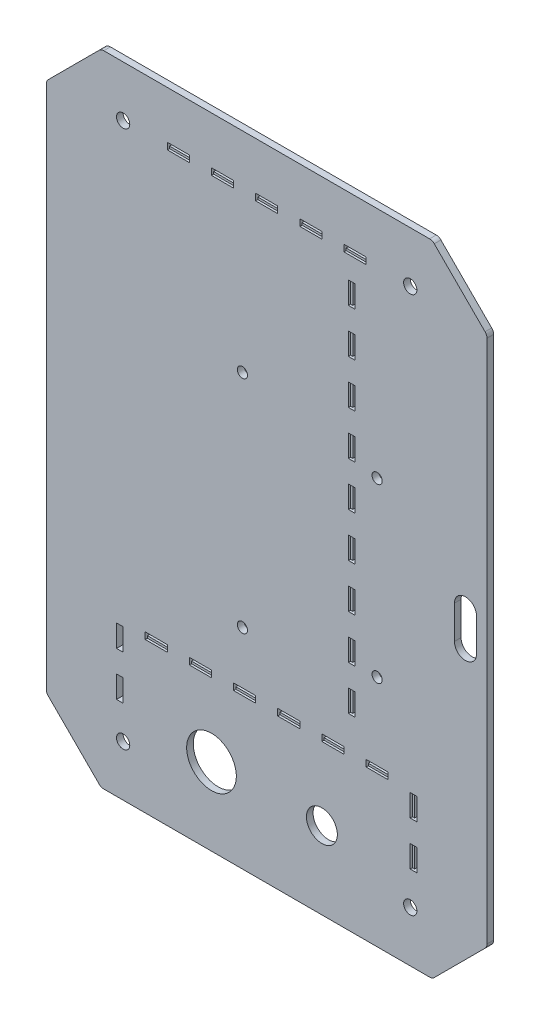
SolidWorks part; units mm, degrees
ref_plane "Plan de face" through (0, 0, 0) normal (0, 0, 1) x (1, 0, 0)
ref_plane "Plan de dessus" through (0, 0, 0) normal (0, 1, 0) x (1, 0, 0)
ref_plane "Plan de droite" through (0, 0, 0) normal (1, 0, 0) x (0, 0, -1)
sketch "Esquisse1" plane through (0, 0, 0) normal (0, 0, 1) x (1, 0, 0)
  line L0 (-99.7487, 120) -> (-75, 144.7487)
  line L1 (-75, 144.7487) -> (75, 144.7487)
  line L2 (-99.7487, 120) -> (-99.7487, -120)
  line L3 (-75, -144.7487) -> (75, -144.7487)
  line L4 (99.7487, 120) -> (99.7487, -120)
  line L5 (75, 144.7487) -> (99.7487, 120)
  line L6 (99.7487, -120) -> (75, -144.7487)
  line L7 (-87.3744, 132.3744) -> (87.3744, -132.3744) construction
  line L8 (-99.7487, -120) -> (-75, -144.7487)
  line L9 (-87.3744, -132.3744) -> (87.3744, 132.3744) construction
  point P0 (0, 0)
  point P14 (0, 0)
  dimension "D1" = 240
  dimension "D2" = 150
  dimension "D3" = 35
  dimension "D4" = 135
  dimension "D5" = 135
extrude "Base" add sketch "Esquisse1" along normal blind 3
sketch "Esquisse2" plane through (0, 0, 3) normal (0, 0, 1) x (1, 0, 0)
  line L0 (-99.7487, 0) -> (99.7487, 0) construction
  line L1 (-99.7487, 120) -> (-99.7487, -120) construction
  line L2 (99.7487, -120) -> (99.7487, 120) construction
  line L3 (0, 144.7487) -> (0, -144.7487) construction
  line L4 (75, 144.7487) -> (-75, 144.7487) construction
  line L5 (-75, -144.7487) -> (75, -144.7487) construction
  line L11 (-67.1213, 123.8701) -> (-62.8787, 119.6274) construction
  line L12 (-67.1213, 119.6274) -> (-62.8787, 123.8701) construction
  circle A0 centre (-65, 121.7487) radius 3
  circle A1 centre (65, 121.7487) radius 3
  circle A2 centre (65, -121.7487) radius 3
  circle A3 centre (-65, -121.7487) radius 3
  point P12 (-65, 121.7487)
  dimension "D5" = 6
  dimension "D3" = 23
  dimension "D4" = 65
extrude "Perçage profilé" cut sketch "Esquisse2" against normal blind 5
sketch "Esquisse3" plane through (0, 0, 0) normal (0, 0, -1) x (-1, 0, 0)
  line L0 (45, 0) -> (-45, 0) construction
  line L6 (75, -144.7487) -> (-75, -144.7487) construction
  line L7 (45, 45) -> (45, -45) construction
  line L8 (45, -45) -> (-45, -45) construction
  line L9 (-45, -45) -> (-45, 45) construction
  line L10 (-45, 45) -> (45, 45) construction
  line L11 (-99.7487, -120) -> (-99.7487, 120) construction
  circle A4 centre (-50, 39) radius 2.3
  circle A5 centre (11, 50) radius 2.3
  circle A6 centre (-50, -39) radius 2.3
  circle A7 centre (11, -50) radius 2.3
  point P16 (-99.7487, 0)
  point P19 (0, -144.7487)
  point P20 (0, 0)
  point P22 (0, -45)
  dimension "D3" = 4.6
  dimension "D8" = 4.6
  dimension "D1" = 90
  dimension "D2" = 90
  dimension "D4" = 5
  dimension "D5" = 6
  dimension "D6" = 34
  dimension "D7" = 5
extrude "Perçage Lidar" cut sketch "Esquisse3" against normal through all
sketch "Esquisse4" plane through (0, 0, 0) normal (0, 0, -1) x (-1, 0, 0)
  line L0 (75, -144.7487) -> (-75, -144.7487) construction
  line L1 (0, -144.7487) -> (0, -86.7053) construction
  circle A0 centre (25, -109.7487) radius 11.25
  dimension "D1" = 22.5
  dimension "D2" = 35
  dimension "D3" = 25
extrude "Perçage bouton d'arret d'urgence" cut sketch "Esquisse4" against normal through all
sketch "Esquisse5" plane through (0, 0, 0) normal (0, 0, -1) x (-1, 0, 0)
  line L0 (0, -59.6223) -> (0, -144.7487) construction
  line L1 (75, -144.7487) -> (-75, -144.7487) construction
  circle A0 centre (-25, -109.7487) radius 7
  dimension "D1" = 14
  dimension "D2" = 25
  dimension "D3" = 35
extrude "Perçage tirette" cut sketch "Esquisse5" against normal through all
sketch "Esquisse7" plane through (0, 0, 0) normal (0, 0, -1) x (-1, 0, 0)
  line L6 (-90, 7.5) -> (-90, -7.5) construction
  line L7 (-85, 7.5) -> (-85, -7.5)
  line L8 (-95, 7.5) -> (-95, -7.5)
  line L9 (-99.7487, -120) -> (-99.7487, 120) construction
  arc A2 (-85, 7.5) -> (-95, 7.5) centre (-90, 7.5) ccw
  arc A3 (-95, -7.5) -> (-85, -7.5) centre (-90, -7.5) ccw
  circle A4 centre (-50, -39) radius 2.3 construction
  point P7 (-90, 0)
  point P23 (-99.7487, 0)
  dimension "D4" = 5
  dimension "D1" = 15
  dimension "D5" = 40
extrude "Perçage cable management" cut sketch "Esquisse7" against normal through all
sketch "Sketch1" plane through (0, 0, 0) normal (0, 0, -1) x (-1, 0, 0)
  line L0 (-45, 123.2487) -> (-35, 123.2487)
  line L1 (-45, 123.2487) -> (-45, 120.2487)
  line L2 (-45, 120.2487) -> (-35, 120.2487)
  line L3 (-35, 123.2487) -> (-35, 120.2487)
  line L4 (-75, 121.7487) -> (-55, 121.7487) construction
  line L5 (-45, 121.7487) -> (-35, 121.7487) construction
  line L6 (-25, 123.2487) -> (-25, 120.2487)
  line L7 (-25, 123.2487) -> (-15, 123.2487)
  line L8 (-15, 123.2487) -> (-15, 120.2487)
  line L9 (-25, 120.2487) -> (-15, 120.2487)
  line L10 (-5, 123.2487) -> (-5, 120.2487)
  line L11 (-5, 123.2487) -> (5, 123.2487)
  line L12 (5, 123.2487) -> (5, 120.2487)
  line L13 (-5, 120.2487) -> (5, 120.2487)
  line L14 (15, 123.2487) -> (15, 120.2487)
  line L15 (15, 123.2487) -> (25, 123.2487)
  line L16 (25, 123.2487) -> (25, 120.2487)
  line L17 (15, 120.2487) -> (25, 120.2487)
  line L18 (35, 123.2487) -> (35, 120.2487)
  line L19 (35, 123.2487) -> (45, 123.2487)
  line L20 (45, 123.2487) -> (45, 120.2487)
  line L21 (35, 120.2487) -> (45, 120.2487)
  line L22 (0, 0) -> (0, -37.251) construction
  line L23 (-68, -106.7487) -> (-65, -106.7487)
  line L24 (-68, -106.7487) -> (-68, -96.7487)
  line L25 (-68, -96.7487) -> (-65, -96.7487)
  line L26 (-65, -106.7487) -> (-65, -96.7487)
  line L27 (-66.5, -106.7487) -> (-66.5, -96.7487) construction
  line L28 (-40, 90.2487) -> (-40, 80.2487)
  line L29 (-40, 110.2487) -> (-37, 110.2487)
  line L30 (-68, -86.7487) -> (-68, -76.7487)
  line L31 (-68, -86.7487) -> (-65, -86.7487)
  line L32 (-65, -86.7487) -> (-65, -76.7487)
  line L33 (-68, -76.7487) -> (-65, -76.7487)
  line L34 (68, -86.7487) -> (65, -86.7487)
  line L35 (65, -86.7487) -> (65, -76.7487)
  line L36 (68, -76.7487) -> (65, -76.7487)
  line L37 (68, -86.7487) -> (68, -76.7487)
  line L38 (68, -96.7487) -> (65, -96.7487)
  line L39 (65, -106.7487) -> (65, -96.7487)
  line L40 (68, -106.7487) -> (65, -106.7487)
  line L41 (68, -106.7487) -> (68, -96.7487)
  line L42 (-35, -76.7487) -> (-35, -73.7487)
  line L43 (-55, -76.7487) -> (-45, -76.7487)
  line L44 (-55, -76.7487) -> (-55, -73.7487)
  line L45 (-55, -73.7487) -> (-45, -73.7487)
  line L46 (-45, -76.7487) -> (-45, -73.7487)
  line L47 (-35, -76.7487) -> (-25, -76.7487)
  line L48 (-25, -76.7487) -> (-25, -73.7487)
  line L49 (-35, -73.7487) -> (-25, -73.7487)
  line L50 (-15, -76.7487) -> (-15, -73.7487)
  line L51 (-15, -76.7487) -> (-5, -76.7487)
  line L52 (-5, -76.7487) -> (-5, -73.7487)
  line L53 (-15, -73.7487) -> (-5, -73.7487)
  line L54 (5, -76.7487) -> (5, -73.7487)
  line L55 (5, -76.7487) -> (15, -76.7487)
  line L56 (15, -76.7487) -> (15, -73.7487)
  line L57 (5, -73.7487) -> (15, -73.7487)
  line L58 (25, -76.7487) -> (25, -73.7487)
  line L59 (25, -76.7487) -> (35, -76.7487)
  line L60 (35, -76.7487) -> (35, -73.7487)
  line L61 (25, -73.7487) -> (35, -73.7487)
  line L62 (45, -76.7487) -> (45, -73.7487)
  line L63 (45, -76.7487) -> (55, -76.7487)
  line L64 (55, -76.7487) -> (55, -73.7487)
  line L65 (45, -73.7487) -> (55, -73.7487)
  line L66 (-40, 110.2487) -> (-40, 100.2487)
  line L67 (-40, 100.2487) -> (-37, 100.2487)
  line L68 (-37, 110.2487) -> (-37, 100.2487)
  line L69 (-40, 90.2487) -> (-37, 90.2487)
  line L70 (-37, 90.2487) -> (-37, 80.2487)
  line L71 (-40, 80.2487) -> (-37, 80.2487)
  line L72 (-40, 70.2487) -> (-40, 60.2487)
  line L73 (-40, 70.2487) -> (-37, 70.2487)
  line L74 (-37, 70.2487) -> (-37, 60.2487)
  line L75 (-40, 60.2487) -> (-37, 60.2487)
  line L76 (-40, 50.2487) -> (-40, 40.2487)
  line L77 (-40, 50.2487) -> (-37, 50.2487)
  line L78 (-37, 50.2487) -> (-37, 40.2487)
  line L79 (-40, 40.2487) -> (-37, 40.2487)
  line L80 (-40, 30.2487) -> (-40, 20.2487)
  line L81 (-40, 30.2487) -> (-37, 30.2487)
  line L82 (-37, 30.2487) -> (-37, 20.2487)
  line L83 (-40, 20.2487) -> (-37, 20.2487)
  line L84 (-40, 10.2487) -> (-40, 0.2487)
  line L85 (-40, 10.2487) -> (-37, 10.2487)
  line L86 (-37, 10.2487) -> (-37, 0.2487)
  line L87 (-40, 0.2487) -> (-37, 0.2487)
  line L88 (-40, -9.7513) -> (-40, -19.7513)
  line L89 (-40, -9.7513) -> (-37, -9.7513)
  line L90 (-37, -9.7513) -> (-37, -19.7513)
  line L91 (-40, -19.7513) -> (-37, -19.7513)
  line L92 (-40, -29.7513) -> (-40, -39.7513)
  line L93 (-40, -29.7513) -> (-37, -29.7513)
  line L94 (-37, -29.7513) -> (-37, -39.7513)
  line L95 (-40, -39.7513) -> (-37, -39.7513)
  line L96 (-40, -49.7513) -> (-40, -59.7513)
  line L97 (-40, -49.7513) -> (-37, -49.7513)
  line L98 (-37, -49.7513) -> (-37, -59.7513)
  line L99 (-40, -59.7513) -> (-37, -59.7513)
  point P53 (-100.1879, -120)
  dimension "D1" = 3
  dimension "D2" = 10
  dimension "D3" = 10
  dimension "D4" = 3
  dimension "D5" = 10
  dimension "D6" = 3
  dimension "D7" = 10
  dimension "D8" = 65
  dimension "D9" = 10
  dimension "D10" = 10
  dimension "D11" = 3
extrude "Cut-Extrude1" cut sketch "Sketch1" against normal through all
sketch "Esquisse8" plane through (0, 0, 3) normal (0, 0, 1) x (1, 0, 0)
  line L1 (-69.7487, 24.5) -> (-69.7487, -24.5) construction
  line L2 (-69.7487, 0) -> (-99.7487, 0) construction
  line L3 (-99.7487, 120) -> (-99.7487, -120) construction
  circle A0 centre (-69.7487, 24.5) radius 2.65
  circle A1 centre (-69.7487, -24.5) radius 2.65
  dimension "D1" = 5.3
  dimension "D2" = 5.3
  dimension "D3" = 49
  dimension "D4" = 30
sketch "Esquisse9" plane through (0, 0, 3) normal (0, 0, 1) x (1, 0, 0)
  line L0 (-53.7487, 17.25) -> (-53.7487, -17.25) construction
  line L1 (-99.7487, 0) -> (-53.7487, 0) construction
  line L2 (-99.7487, 120) -> (-99.7487, -120) construction
  circle A0 centre (-53.7487, 17.25) radius 2.1
  circle A1 centre (-53.7487, -17.25) radius 2.1
  point P11 (-53.7487, 0)
  dimension "D1" = 4.2
  dimension "D2" = 4.2
  dimension "D3" = 34.5
  dimension "D4" = 46
fillet "Congé1" radius 3 8 edges at (99.7487, -120, 1.5) (75, -144.7487, 1.5) (-75, -144.7487, 1.5) (-99.7487, -120, 1.5) (-99.7487, 120, 1.5) (-75, 144.7487, 1.5) (99.7487, 120, 1.5) (75, 144.7487, 1.5)
sketch "Esquisse10" plane through (0, 0, 0) normal (0, 0, -1) x (-1, 0, 0)
  line L0 (45, 120.2487) -> (45, 123.2487) construction
  line L1 (-45, 120.2487) -> (45, 120.2487)
  line L2 (-45, 120.2487) -> (-45, 121.2487)
  line L3 (-45, 121.2487) -> (45, 121.2487)
  line L4 (45, 120.2487) -> (45, 121.2487)
  line L5 (-40, -59.7513) -> (-37, -59.7513) construction
  line L6 (-37, 110.2487) -> (-38, 110.2487)
  line L7 (-37, 110.2487) -> (-37, -59.7513)
  line L8 (-37, -59.7513) -> (-38, -59.7513)
  line L9 (-38, 110.2487) -> (-38, -59.7513)
  line L10 (55, -76.7487) -> (55, -73.7487) construction
  line L11 (-55, -76.7487) -> (55, -76.7487)
  line L12 (-55, -76.7487) -> (-55, -75.7487)
  line L13 (-55, -75.7487) -> (55, -75.7487)
  line L14 (55, -76.7487) -> (55, -75.7487)
  line L15 (65, -106.7487) -> (68, -106.7487) construction
  line L16 (65, -76.7487) -> (66, -76.7487)
  line L17 (65, -76.7487) -> (65, -106.7487)
  line L18 (65, -106.7487) -> (66, -106.7487)
  line L19 (66, -76.7487) -> (66, -106.7487)
  line L20 (-68, -106.7487) -> (-65, -106.7487) construction
  line L21 (-65, -76.7487) -> (-66, -76.7487)
  line L22 (-65, -76.7487) -> (-65, -106.7487)
  line L23 (-65, -106.7487) -> (-66, -106.7487)
  line L24 (-66, -76.7487) -> (-66, -106.7487)
  dimension "D1" = 1
extrude "Boss.-Extru.1" add sketch "Esquisse10" against normal blind 2
